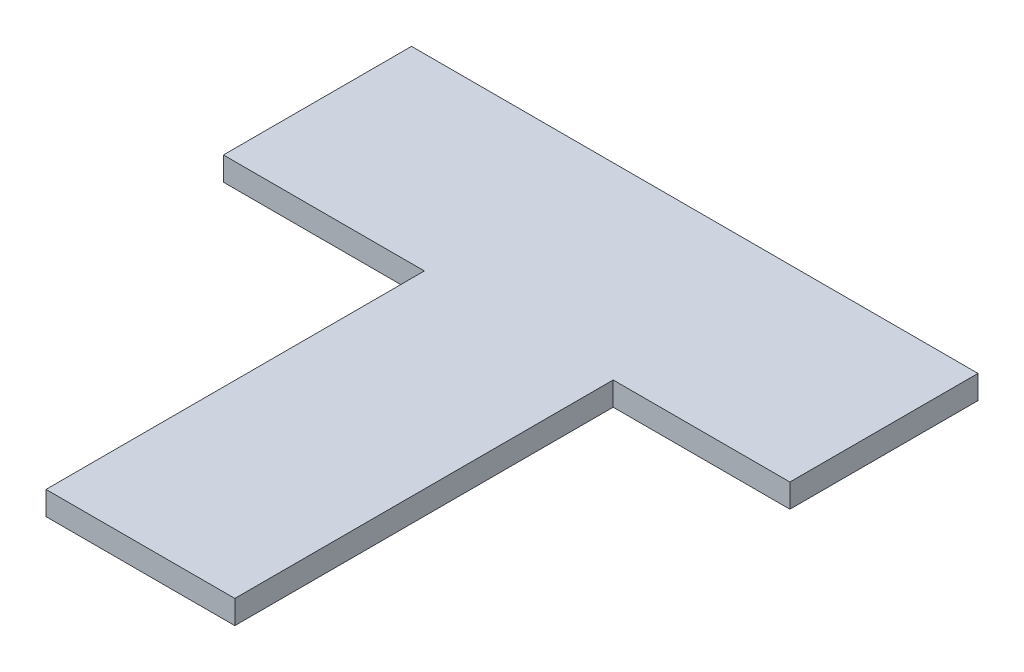
SolidWorks part; units mm, degrees
ref_plane "Front Plane" through (0, 0, 0) normal (0, 0, 1) x (1, 0, 0)
ref_plane "Top Plane" through (0, 0, 0) normal (0, 1, 0) x (1, 0, 0)
ref_plane "Right Plane" through (0, 0, 0) normal (1, 0, 0) x (0, 0, -1)
sketch "Sketch1" plane through (0, 0, 0) normal (0, 1, 0) x (1, 0, 0)
  line L0 (25.4, 50.8958) -> (49.1706, 50.8958)
  line L1 (0, 0) -> (25.4, 0)
  line L2 (0, 0) -> (0, 50.8958)
  line L4 (25.4, 0) -> (25.4, 50.8958)
  line L5 (-27.0294, 50.8958) -> (0, 50.8958)
  line L6 (-27.0294, 50.8958) -> (-27.0294, 76.2)
  line L7 (-27.0294, 76.2) -> (49.1706, 76.2)
  line L8 (49.1706, 50.8958) -> (49.1706, 76.2)
  dimension "D1" = 76.2
  dimension "D2" = 76.2
  dimension "D3" = 25.3042
  dimension "D4" = 25.4
extrude "Boss-Extrude1" add sketch "Sketch1" along normal blind 3.175
